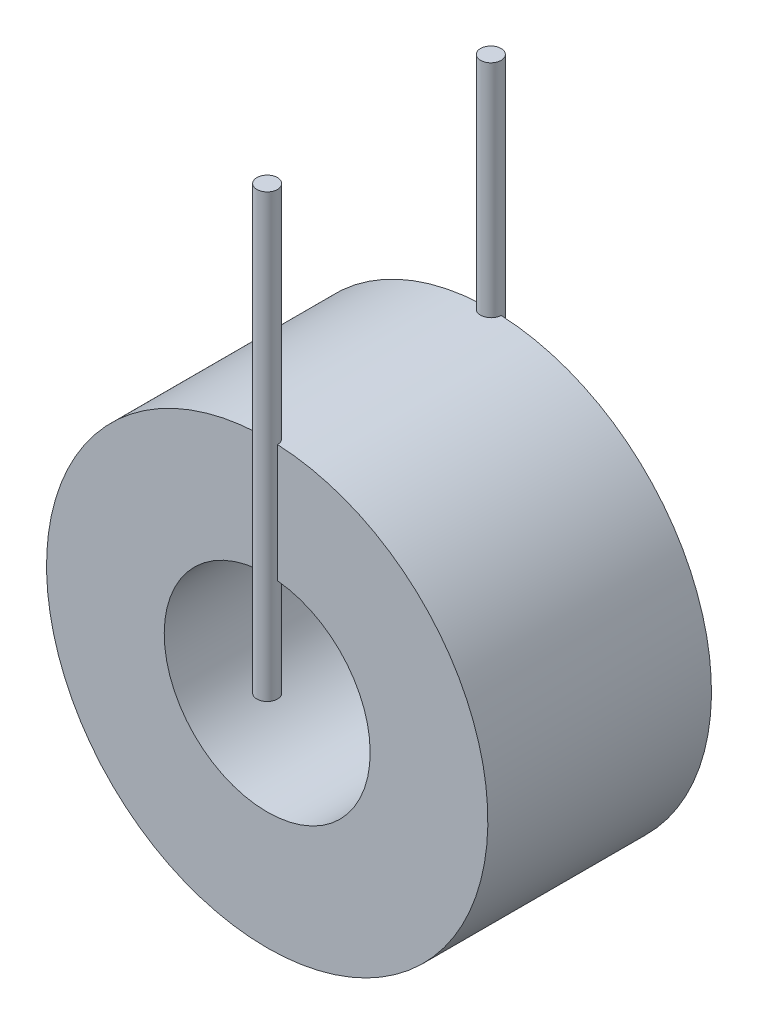
SolidWorks part; units mm, degrees
ref_plane "前视基准面" through (0, 0, 0) normal (0, 0, 1) x (1, 0, 0)
ref_plane "上视基准面" through (0, 0, 0) normal (0, 1, 0) x (1, 0, 0)
ref_plane "右视基准面" through (0, 0, 0) normal (1, 0, 0) x (0, 0, -1)
sketch "草图1" plane through (0, 0, 0) normal (0, 0, 1) x (1, 0, 0)
  circle A0 centre (0, 0) radius 7.5
  circle A1 centre (0, 0) radius 3.5
  dimension "D1" = 15
  dimension "D2" = 7
extrude "凸台-拉伸1" add sketch "草图1" along normal blind 3.8 and the other way blind 3.8
sketch "草图3" plane through (0, 0, 0) normal (0, 1, 0) x (1, 0, 0)
  line L0 (0, 5.9948) -> (0, -5.6382) construction
  line L1 (7.5, 3.8) -> (-7.5, 3.8) construction
  line L2 (-8.3269, 0) -> (9.5616, 0) construction
  circle A0 centre (0, 3.8) radius 0.35
  circle A1 centre (0, -3.8) radius 0.35
  dimension "D1" = 0.7
extrude "凸台-拉伸2" add sketch "草图3" along normal blind 15
